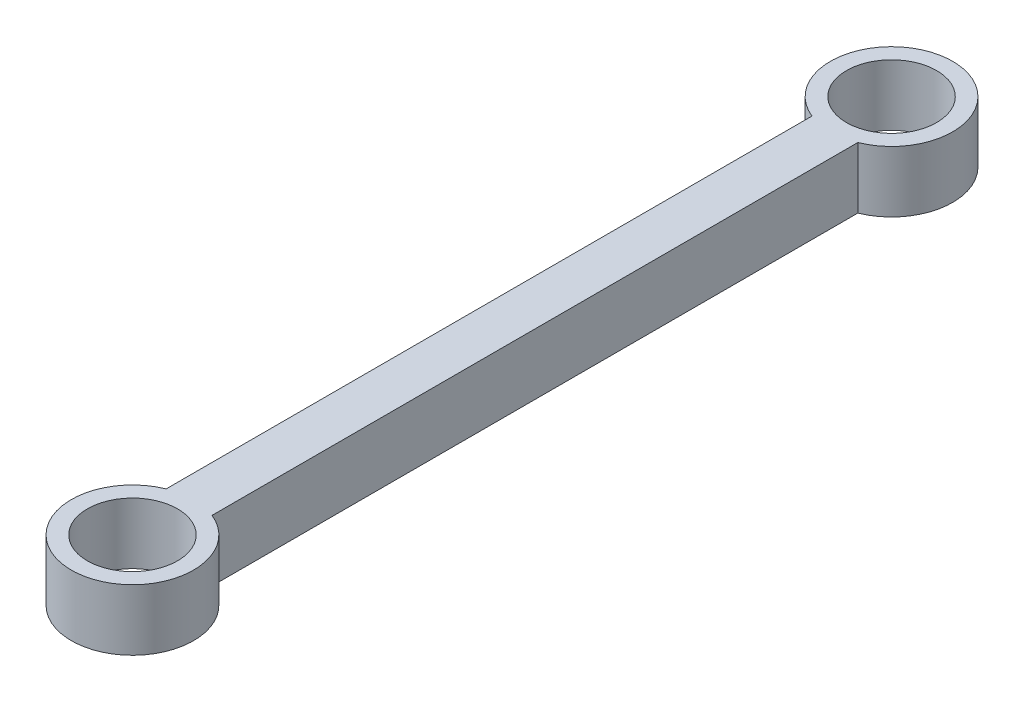
SolidWorks part; units mm, degrees
ref_plane "Front Plane" through (0, 0, 0) normal (0, 0, 1) x (1, 0, 0)
ref_plane "Top Plane" through (0, 0, 0) normal (0, 1, 0) x (1, 0, 0)
ref_plane "Right Plane" through (0, 0, 0) normal (1, 0, 0) x (0, 0, -1)
sketch "Sketch1" plane through (0, 0, 0) normal (0, 1, 0) x (1, 0, 0)
  line L0 (0, 0) -> (0, 49.67) construction
  line L1 (-1.5, 45.9619) -> (-1.5, 3.7081)
  line L2 (1.5, 45.9619) -> (1.5, 3.7081)
  circle A0 centre (0, 49.67) radius 2.95
  circle A1 centre (0, 0) radius 2.95
  arc A2 (1.5, 45.9619) -> (-1.5, 45.9619) centre (0, 49.67) ccw
  arc A3 (-1.5, 3.7081) -> (1.5, 3.7081) centre (0, 0) ccw
  dimension "D2" = 5.9
  dimension "D3" = 5.9
  dimension "D4" = 8
  dimension "D5" = 8
  dimension "D1" = 49.67
  dimension "D6" = 1.5
  dimension "D7" = 1.5
extrude "Boss-Extrude1" add sketch "Sketch1" along normal blind 4
